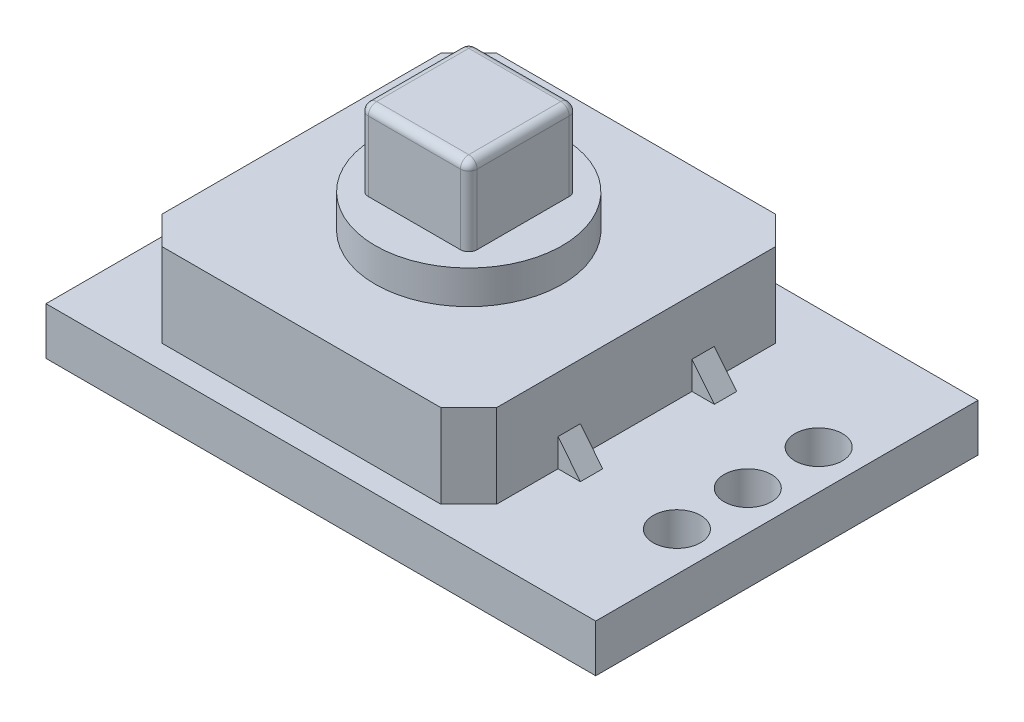
SolidWorks part; units mm, degrees
ref_plane "Спереди" through (0, 0, 0) normal (0, 0, 1) x (1, 0, 0)
ref_plane "Сверху" through (0, 0, 0) normal (0, 1, 0) x (1, 0, 0)
ref_plane "Справа" through (0, 0, 0) normal (1, 0, 0) x (0, 0, -1)
sketch "Эскиз1" plane through (0, 0, 0) normal (0, 1, 0) x (1, 0, 0)
  line L1 (-9.85, 6.85) -> (9.85, 6.85)
  line L2 (-9.85, 6.85) -> (-9.85, -6.85)
  line L3 (-9.85, -6.85) -> (9.85, -6.85)
  line L4 (9.85, 6.85) -> (9.85, -6.85)
  line L5 (-9.85, 6.85) -> (9.85, -6.85) construction
  line L6 (-9.85, -6.85) -> (9.85, 6.85) construction
  point P0 (0, 0)
  dimension "D1" = 19.7
  dimension "D2" = 13.7
extrude "Бобышка-Вытянуть1" add sketch "Эскиз1" along normal blind 1.7
sketch "Эскиз2" plane through (0, 1.7, 0) normal (0, 1, 0) x (1, 0, 0)
  line L0 (-9.85, 6.85) -> (-9.85, -6.85) construction
  line L1 (-7.55, 6) -> (4.45, 6)
  line L2 (-7.55, 6) -> (-7.55, -6)
  line L3 (-7.55, -6) -> (4.45, -6)
  line L4 (4.45, 6) -> (4.45, -6)
  line L5 (-7.55, 6) -> (4.45, -6) construction
  line L6 (-7.55, -6) -> (4.45, 6) construction
  point P0 (-1.55, 0)
  point P9 (-9.85, 0)
  dimension "D1" = 12
  dimension "D2" = 12
  dimension "D3" = 2.3
extrude "Бобышка-Вытянуть2" add sketch "Эскиз2" along normal blind 3
sketch "Эскиз3" plane through (0, 4.7, 0) normal (0, -1, 0) x (-1, 0, 0)
  line L1 (3.5, 1.95) -> (-0.4, 1.95)
  line L2 (3.5, 1.95) -> (3.5, -1.95)
  line L3 (3.5, -1.95) -> (-0.4, -1.95)
  line L4 (-0.4, 1.95) -> (-0.4, -1.95)
  line L5 (3.5, 1.95) -> (-0.4, -1.95) construction
  line L6 (3.5, -1.95) -> (-0.4, 1.95) construction
  point P0 (1.55, 0)
  dimension "D1" = 3.9
extrude "Бобышка-Вытянуть3" add sketch "Эскиз3" against normal blind 4
sketch "Эскиз4" plane through (0, 4.7, 0) normal (0, 1, 0) x (1, 0, 0)
  line L0 (-3.5, 1.95) -> (0.4, 1.95) construction
  line L1 (-3.5, -1.95) -> (-3.5, 1.95) construction
  circle A0 centre (-1.55, 0) radius 3.35
  point P5 (-1.55, 1.95)
  point P8 (-3.5, 0)
  dimension "D1" = 6.7
extrude "Бобышка-Вытянуть4" add sketch "Эскиз4" along normal blind 1.2
sketch "Эскиз6" plane through (0, 1.7, 0) normal (0, 1, 0) x (1, 0, 0)
  line L0 (9.85, -6.85) -> (9.85, 6.85) construction
  circle A0 centre (8.45, -2.54) radius 0.85
  circle A1 centre (8.45, 0) radius 0.85
  circle A2 centre (8.45, 2.54) radius 0.85
  point P9 (9.85, 0)
  dimension "D3" = 1.7
  dimension "D2" = 2.54
  dimension "D4" = 1.4
  dimension "D1" = 3
extrude "Вырез-Вытянуть1" cut sketch "Эскиз6" against normal through all
chamfer "Фаска1" distance 1 angle 45 4 edges at (-7.55, 3.2, -6) (-7.55, 3.2, 6) (4.45, 3.2, -6) (4.45, 3.2, 6)
fillet "Скругление2" radius 0.3 8 edges at (-1.55, 8.7, 1.95) (-3.5, 8.7, 0) (-1.55, 8.7, -1.95) (0.4, 8.7, 0) (-3.5, 7.3, 1.95) (0.4, 7.3, 1.95) (-3.5, 7.3, -1.95) (0.4, 7.3, -1.95)
ref_plane "Плоскость3" through (0, 0, 0) normal (0, 0, 1) x (1, 0, 0)
sketch "Эскиз7" plane through (0, 0, 0) normal (0, 0, 1) x (1, 0, 0)
  line L0 (-9.85, 1.7) -> (9.85, 1.7) construction
  line L1 (-7.55, 1.7) -> (-7.55, 4.7) construction
  line L2 (-8.35, 1.7) -> (-7.55, 1.7)
  line L3 (-7.55, 1.7) -> (-7.55, 2.7)
  line L4 (-8.35, 1.7) -> (-7.55, 2.7)
  line L5 (4.45, 2.7) -> (4.45, 1.7)
  line L9 (4.45, 1.7) -> (5.25, 1.7)
  line L10 (5.25, 1.7) -> (4.45, 2.7)
  line L11 (-7.55, 0) -> (-7.55, -1)
  line L12 (-9.85, 0) -> (9.85, 0) construction
  line L13 (-7.55, -1) -> (-8.35, -1)
  line L14 (-8.35, -1) -> (-8.35, 0)
  line L15 (-8.35, 0) -> (-7.55, 0)
  line L16 (4.45, 0) -> (4.45, -1)
  line L17 (4.45, -1) -> (5.25, -1)
  line L18 (5.25, -1) -> (5.25, 0)
  line L19 (5.25, 0) -> (4.45, 0)
  dimension "D1" = 1
  dimension "D2" = 0.8
  dimension "D3" = 1
extrude "Бобышка-Вытянуть6" add sketch "Эскиз7" along normal blind 0.8 from offset 2
extrude "Бобышка-Вытянуть7" add sketch "Эскиз7<3>" against normal blind 0.8 from offset 2 offset against normal yes
sketch "Эскиз7<3>" plane through (0, 0, 0) normal (0, 0, 1) x (1, 0, 0) same geometry as "Эскиз7"
fillet "Скругление3" radius 0.4 16 edges at (4.45, -0.5, 2.8) (4.45, -0.5, 2) (4.45, -0.5, -2) (4.45, -0.5, -2.8) (5.25, -0.5, -2.8) (5.25, -0.5, 2.8) (5.25, -0.5, 2) (5.25, -0.5, -2) (-7.55, -0.5, -2) (-7.55, -0.5, -2.8) (-8.35, -0.5, -2.8) (-8.35, -0.5, -2) (-8.35, -0.5, 2.8) (-8.35, -0.5, 2) (-7.55, -0.5, 2) (-7.55, -0.5, 2.8)
fillet "Скругление4" radius 0.1 16 edges at (-7.6672, -1, 2.1172) (-8.2328, -1, 2.1172) (-8.2328, -1, 2.6828) (-7.6672, -1, 2.6828) (-8.2328, -1, -2.6828) (-8.2328, -1, -2.1172) (-7.6672, -1, -2.1172) (-7.6672, -1, -2.6828) (5.1328, -1, -2.6828) (4.5672, -1, -2.6828) (4.5672, -1, -2.1172) (5.1328, -1, -2.1172) (5.1328, -1, 2.1172) (4.5672, -1, 2.1172) (4.5672, -1, 2.6828) (5.1328, -1, 2.6828) curvature continuous yes
